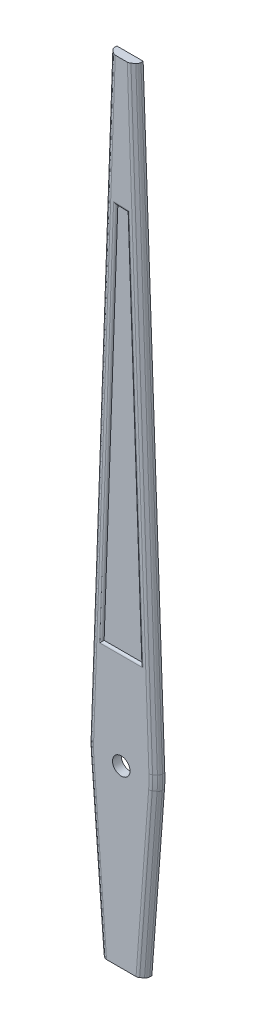
SolidWorks part; units mm, degrees
ref_plane "Front" through (0, 0, 0) normal (0, 0, 1) x (1, 0, 0)
ref_plane "Top" through (0, 0, 0) normal (0, 1, 0) x (1, 0, 0)
ref_plane "Right" through (0, 0, 0) normal (1, 0, 0) x (0, 0, -1)
sketch "Эскиз1" plane through (0, 0, 0) normal (0, 0, 1) x (1, 0, 0)
  line L0 (0, -4.0861) -> (0, 11.4075) construction
  line L1 (-6.6602, 0) -> (8.2395, 0) construction
  line L2 (-0.7941, 0.1659) -> (-0.3, 14)
  line L3 (-0.3, 14) -> (0.3, 14)
  line L4 (-0.7876, -0.1655) -> (-0.5, -4)
  line L5 (-0.5, -4) -> (0.5, -4)
  line L6 (0.7876, -0.1655) -> (0.5, -4)
  line L7 (0.7941, 0.1659) -> (0.3, 14)
  circle A0 centre (0, 0) radius 0.2
  arc A1 (0.7876, -0.1655) -> (0.7941, 0.1659) centre (-2.204, 0.0588) ccw
  arc A2 (-0.7941, 0.1659) -> (-0.7876, -0.1655) centre (2.204, 0.0588) ccw
  point P13 (0, -4)
  point P15 (0, 14)
  point P17 (0.8, 0)
  point P20 (-0.8, 0)
  dimension "D1" = 0.4
  dimension "D7" = 3
  dimension "D2" = 0.8
  dimension "D3" = 0.3
  dimension "D4" = 0.5
  dimension "D5" = 4
  dimension "D6" = 14
extrude "Бобышка-Вытянуть1" add sketch "Эскиз1" along normal blind 0.2
chamfer "Фаска1" distance 0.1 angle 52 6 edges at (0.6438, -2.0828, 0.2) (0.7954, 0.0001, 0.2) (0.547, 7.083, 0.2) (-0.6438, -2.0828, 0.2) (-0.7954, 0.0001, 0.2) (-0.547, 7.083, 0.2) first distance on face at (0.6438, -2.0828, 0.1) first distance on face at (0.7931, 0.0001, 0.1) first distance on face at (0.547, 7.083, 0.1) first distance on face at (-0.6438, -2.0828, 0.1) first distance on face at (-0.7931, 0.0001, 0.1) first distance on face at (-0.547, 7.083, 0.1)
sketch "Эскиз2" plane through (0, 0, 0.2) normal (0, 0, 1) x (1, 0, 0)
  line L3 (-0.022, 13.9946) -> (-0.5163, 0.156)
  line L4 (-0.1278, 11.0319) -> (-0.4418, 2.24)
  line L5 (-0.4418, 2.24) -> (0.4418, 2.24)
  line L6 (0.5163, 0.156) -> (0.022, 13.9946)
  line L7 (0.4418, 2.24) -> (0.1282, 11.0227)
  line L8 (-0.3716, -4) -> (0.3716, -4) construction
  line L9 (-0.1278, 11.0319) -> (0.1282, 11.0227)
  point P8 (0, -4)
  dimension "D3" = 6.24
  dimension "D4" = 0.2562
  dimension "D1" = 0.15
  dimension "D2" = 0.15
extrude "Вырез-Вытянуть1" cut sketch "Эскиз2" against normal blind 0.05
fillet "Скругление1" radius 0.1 12 edges at (-0.6438, -2.0828, 0.1) (-0.7954, 0.0001, 0.1) (-0.5158, -2.078, 0.2) (-0.6674, 0.0026, 0.2) (0.6438, -2.0828, 0.1) (0.7954, 0.0001, 0.1) (0.5158, -2.078, 0.2) (0.6674, 0.0026, 0.2) (-0.547, 7.083, 0.1) (-0.419, 7.0807, 0.2) (0.547, 7.083, 0.1) (0.419, 7.0807, 0.2)
fillet "Скругление2" radius 0.05 4 edges at (0.0002, 11.0273, 0.2) (0.285, 6.6314, 0.2) (0, 2.24, 0.2) (-0.2848, 6.6359, 0.2)
